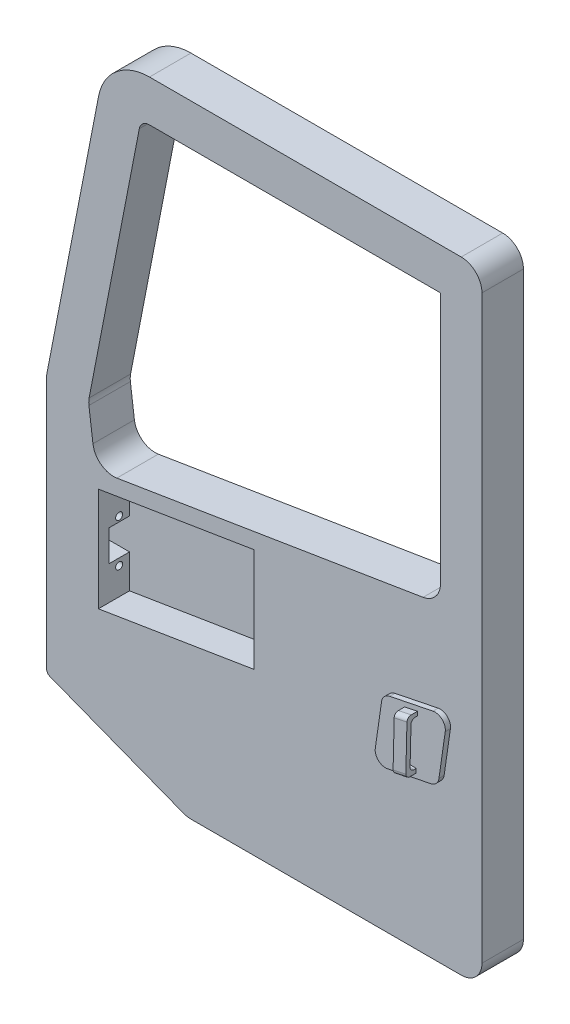
SolidWorks part; units mm, degrees
ref_plane "Front Plane" through (0, 0, 0) normal (0, 0, 1) x (1, 0, 0)
ref_plane "Top Plane" through (0, 0, 0) normal (0, 1, 0) x (1, 0, 0)
ref_plane "Right Plane" through (0, 0, 0) normal (1, 0, 0) x (0, 0, -1)
sketch "Sketch2" plane through (0, 0, 0) normal (0, 0, 1) x (1, 0, 0)
  line L0 (-405.8971, 659.2079) -> (-532.5433, 7.5919)
  line L1 (-179.7693, -762.022) -> (482.6, -762.022)
  line L3 (-281.2299, 761.978) -> (482.6, 761.978)
  line L4 (533.4, -711.222) -> (533.4, 711.178)
  line L5 (-459.8603, -656.939) -> (-452.0517, -645.784) construction
  line L6 (-417.9715, 597.0829) -> (44.1715, -63.1001) construction
  line L8 (-525.2852, -631.9868) -> (-198.1028, -758.5984)
  line L9 (-306.1633, 639.824) -> (-429.1581, 6.9955)
  line L10 (-429.6693, -9.2299) -> (-419.7789, -85.4932)
  line L14 (-281.2299, 660.378) -> (431.8, 660.378)
  line L15 (389.1621, -6.9365) -> (-361.2381, -129.0997)
  line L16 (431.7995, 43.2033) -> (431.8, 660.378)
  line L17 (431.8, -660.422) -> (431.8, 660.378) construction
  line L18 (-170.2829, -660.422) -> (431.8, -660.422) construction
  line L20 (-354.461, -589.1496) -> (-170.2829, -660.422) construction
  line L21 (-55.5325, -79.3316) -> (521.0599, 744.3665) construction
  line L22 (-306.1633, 639.824) -> (-430.7268, -1.0758) construction
  line L23 (-430.7268, -1.0758) -> (-354.461, -589.1496) construction
  line L24 (-416.9351, -673.9156) -> (-198.1028, -758.5984) construction
  line L25 (-179.7693, -762.022) -> (482.6, -762.022)
  line L27 (-281.2299, 761.978) -> (482.6, 761.978)
  line L28 (533.4, -711.222) -> (533.4, 711.178)
  line L29 (-459.8603, -656.939) -> (521.0599, 744.3665) construction
  line L30 (-417.9715, 597.0829) -> (521.0843, -744.3822) construction
  line L31 (-533.4018, 0.6529) -> (-448.7537, -652.0554) construction
  line L34 (-281.2299, 761.978) -> (482.6, 761.978)
  line L35 (-533.4018, 0.6529) -> (-533.4018, -620.1427)
  line L36 (-179.7693, -762.022) -> (482.6, -762.022)
  line L37 (533.4, 711.178) -> (533.4, -711.222)
  line L38 (-417.9715, 597.0829) -> (521.0843, -744.3822) construction
  line L39 (-460.0617, -657.2267) -> (521.0599, 744.3665) construction
  arc A0 (-405.8971, 659.2079) -> (-281.2299, 761.978) centre (-281.2299, 634.978) cw
  arc A2 (-532.5433, 7.5919) -> (-533.4018, 0.6529) centre (-482.6765, -2.1001) ccw
  arc A3 (533.4, 711.178) -> (482.6, 761.978) centre (482.6, 711.178) ccw
  arc A4 (482.6, -762.022) -> (533.4, -711.222) centre (482.6, -711.222) ccw
  arc A5 (-198.1028, -758.5984) -> (-179.7693, -762.022) centre (-179.7693, -711.222) ccw
  arc A7 (-354.461, -589.1496) -> (-354.461, -589.1496) centre (-354.461, -589.1496) ccw
  arc A8 (-170.2829, -660.422) -> (-170.2829, -660.422) centre (-170.2829, -660.422) ccw
  arc A9 (431.8, -660.422) -> (431.8, -660.422) centre (431.8, -660.422) ccw
  arc A10 (431.8, 660.378) -> (431.8, 660.378) centre (431.8, 660.378) ccw
  arc A11 (-306.1633, 639.824) -> (-281.2299, 660.378) centre (-281.2299, 634.978) cw
  arc A12 (-429.1581, 6.9955) -> (-429.6693, -9.2299) centre (-379.2912, -2.6964) ccw
  arc A13 (-430.7268, -1.0758) -> (-430.7268, -1.0758) centre (-430.7268, -1.0758) ccw construction
  arc A14 (431.7995, 43.2033) -> (389.1621, -6.9365) centre (380.9995, 43.2034) cw
  arc A15 (-419.7789, -85.4932) -> (-361.2381, -129.0997) centre (-369.4008, -78.9598) ccw
  arc A16 (-448.7537, -652.0554) -> (-416.9351, -673.9156) centre (-390.71, -601.6569) ccw construction
  arc A17 (-533.4018, -620.1427) -> (-525.2852, -631.9868) centre (-520.7018, -620.1427) ccw
  point P0 (0, 0)
  point P16 (-533.4, -0.0244)
  point P56 (0, 0)
  point P61 (0, 0)
  dimension "D3" = 127
  dimension "D5" = 50.8
  dimension "D6" = 50.8
  dimension "D8" = 50.8
  dimension "D2" = 12.7
  dimension "D1" = 1066.8
  dimension "D4" = 1524
  dimension "D7" = 101.6
extrude "Boss-Extrude1" add sketch "Sketch2" along normal mid plane 101.6 contours L8 A5 L1 A4 L4 A3 L3 A0 L0 A2 A15 L10 A12 L9 A11 L14 L16 A14 L15 region at (29.3865, -188.1823, 0)
sketch "Sketch3" plane through (0, 0, 50.8) normal (0, 0, 1) x (1, 0, 0)
  line L0 (320.1959, -245.101) -> (425.9265, -223.6716)
  line L3 (314.9201, -401.6691) -> (420.6507, -380.2397)
  line L4 (456.113, -252.1835) -> (440.7462, -358.9639)
  line L5 (300.1004, -266.3768) -> (284.7336, -373.1572)
  line L6 (310.4001, -194.8067) -> (287.3499, -354.9772) construction
  line L7 (-487.6326, -408.8312) -> (533.4008, -201.8888) construction
  line L8 (-457.3598, -558.1943) -> (563.6737, -351.2518) construction
  line L9 (461.2461, -216.515) -> (438.1959, -376.6855) construction
  line L10 (373.0612, -234.3863) -> (367.7854, -390.9544) construction
  line L11 (360.2667, -236.9795) -> (354.9908, -393.5476)
  line L12 (385.8558, -231.7931) -> (380.58, -388.3612)
  line L13 (360.3684, -233.9586) -> (355.0926, -390.5267) construction
  line L14 (385.754, -234.814) -> (380.4782, -391.3821) construction
  arc A0 (300.1004, -266.3768) -> (320.1959, -245.101) centre (325.2414, -269.9949) cw
  arc A1 (284.7336, -373.1572) -> (314.9201, -401.6691) centre (309.8746, -376.7752) ccw
  arc A2 (440.7462, -358.9639) -> (420.6507, -380.2397) centre (415.6052, -355.3458) cw
  arc A3 (456.113, -252.1835) -> (425.9265, -223.6716) centre (430.972, -248.5655) ccw
  dimension "D3" = 25.4
  dimension "D1" = 152.4
  dimension "D2" = 152.4
  dimension "D4" = 12.7
  dimension "D5" = 12.7
extrude "Boss-Extrude2" add sketch "Sketch3" along normal blind 12.7 contours L5 A1 L3 L11 L0 A0 | L4 A3 L0 L12 L3 A2 | L12 L0 L11 L3 region at (325.2101, -323.7797, 50.8) region at (370.4233, -312.6704, 50.8) region at (415.6365, -301.561, 50.8)
sketch "Sketch5" plane through (0, 0, 50.8) normal (0, 0, 1) x (1, 0, 0)
  line L0 (-429.6693, -9.2299) -> (-419.7789, -85.4932) construction
  line L1 (389.1621, -6.9365) -> (-361.2381, -129.0997) construction
  line L2 (431.7995, 43.2033) -> (431.8, 660.378) construction
  line L3 (-281.2299, 660.378) -> (431.8, 660.378) construction
  line L4 (-306.1633, 639.824) -> (-429.1581, 6.9955) construction
  line L5 (-429.6693, -9.2299) -> (-419.7789, -85.4932)
  line L6 (-179.7693, -762.022) -> (482.6, -762.022)
  line L12 (-179.7693, -762.022) -> (482.6, -762.022)
  line L18 (389.1621, -6.9365) -> (-361.2381, -129.0997)
  line L19 (431.7995, 43.2033) -> (431.8, 660.378)
  line L20 (-281.2299, 660.378) -> (431.8, 660.378)
  line L21 (-306.1633, 639.824) -> (-429.1581, 6.9955)
  line L28 (387.9598, -243.0291) -> (384.7172, -375.8602)
  line L29 (353.4927, -382.1888) -> (356.7353, -249.3577)
  line L30 (387.9598, -243.0291) -> (356.7353, -249.3577)
  line L31 (384.7172, -375.8602) -> (353.4927, -382.1888)
  line L32 (320.1959, -245.101) -> (425.9265, -223.6716) construction
  line L33 (314.9201, -401.6691) -> (420.6507, -380.2397) construction
  line L34 (320.1959, -245.101) -> (425.9265, -223.6716) construction
  line L35 (314.9201, -401.6691) -> (420.6507, -380.2397) construction
  arc A0 (-419.7789, -85.4932) -> (-361.2381, -129.0997) centre (-369.4008, -78.9598) ccw construction
  arc A1 (389.1621, -6.9365) -> (431.7995, 43.2033) centre (380.9995, 43.2034) ccw construction
  arc A2 (-281.2299, 660.378) -> (-306.1633, 639.824) centre (-281.2299, 634.978) ccw construction
  arc A3 (-429.1581, 6.9955) -> (-429.6693, -9.2299) centre (-379.2912, -2.6964) ccw construction
  arc A4 (-419.7789, -85.4932) -> (-361.2381, -129.0997) centre (-369.4008, -78.9598) ccw
  arc A5 (389.1621, -6.9365) -> (431.7995, 43.2033) centre (380.9995, 43.2034) ccw
  arc A18 (-281.2299, 660.378) -> (-306.1633, 639.824) centre (-281.2299, 634.978) ccw
  arc A19 (-429.1581, 6.9955) -> (-429.6693, -9.2299) centre (-379.2912, -2.6964) ccw
  dimension "D2" = 11.43
  dimension "D3" = 11.43
  dimension "D1" = 0
extrude "Boss-Extrude4" add sketch "Sketch5" along normal blind 38.1 contours L31 L28 L30 L29 region at (370.7262, -312.609, 50.8)
sketch "Sketch6" plane through (393.6581, -9.61, 0) normal (0.9997, -0.0244, 0) x (0, 0, -1)
  line L9 (-63.5, -356.1994) -> (-78.74, -356.1994)
  line L10 (-78.74, -356.1994) -> (-78.74, -243.6487)
  line L11 (-78.74, -243.6487) -> (-63.5, -243.6487)
  line L12 (-63.5, -356.1994) -> (-78.74, -356.1994)
  line L13 (-78.74, -356.1994) -> (-78.74, -243.6487)
  line L14 (-78.74, -243.6487) -> (-63.5, -243.6487)
  line M5 (-63.5, -366.3594) -> (-63.5, -233.4887)
  dimension "D1" = 10.16
extrude "Cut-Extrude6" cut sketch "Sketch6" against normal through all and the other way through all contours L14 L13 L12 M5 region at (386.3385, -309.4447, 71.12)
fillet "Fillet5" radius 10.16 4 edges at (369.1049, -379.0245, 88.9) (369.4394, -365.3242, 78.74) (372.1861, -252.8071, 78.74) (372.3476, -246.1934, 88.9)
sketch "Sketch7" plane through (-533.4018, 59.3738, 0) normal (1, 0, 0) x (0, 0, 1)
  line L0 (0, 821.3958) -> (0, -702.6042) construction
  line L1 (50.8, 821.3958) -> (-50.8, 821.3958) construction
  line L2 (50.8, -702.6042) -> (-50.8, -702.6042) construction
  line L3 (50.8, 58.7209) -> (-50.8, 58.7209) construction
  line L4 (-31.75, 84.1209) -> (31.75, 84.1209)
  line L5 (-31.75, 84.1209) -> (-31.75, 236.5209)
  line L6 (-31.75, 236.5209) -> (31.75, 236.5209)
  line L11 (31.75, 84.1209) -> (31.75, 236.5209)
  line L12 (-31.75, 84.1209) -> (31.75, 236.5209) construction
  line L13 (-31.75, 236.5209) -> (31.75, 84.1209) construction
  line L21 (-31.75, 642.9209) -> (31.75, 642.9209)
  line L28 (-31.75, 642.9209) -> (-31.75, 490.5209)
  line L29 (-31.75, 490.5209) -> (31.75, 490.5209)
  line L30 (31.75, 642.9209) -> (31.75, 490.5209)
  line L31 (-31.75, 642.9209) -> (31.75, 490.5209) construction
  line L32 (-31.75, 490.5209) -> (31.75, 642.9209) construction
  point P6 (0, 160.3209)
  point P13 (0, 566.7209)
  dimension "D1" = 63.5
  dimension "D2" = 152.4
  dimension "D3" = 25.4
  dimension "D4" = 254
extrude "Boss-Extrude5" add sketch "Sketch7" against normal blind 12.7
sketch "Sketch13" plane through (-546.1018, 0, 0) normal (-1, 0, 0) x (0, 0, 1)
  line L0 (0, -24.7471) -> (0, -177.1471) construction
  line L3 (-31.75, -24.7471) -> (31.75, -24.7471) construction
  line L6 (31.75, -177.1471) -> (-31.75, -177.1471) construction
  line L9 (31.75, -100.9471) -> (-31.75, -100.9471) construction
  line L10 (31.75, -24.7471) -> (31.75, -177.1471) construction
  line L11 (-31.75, -177.1471) -> (-31.75, -24.7471) construction
  line L12 (0, -431.1471) -> (0, -583.5471) construction
  line L13 (-31.75, -431.1471) -> (31.75, -431.1471) construction
  line L14 (31.75, -583.5471) -> (-31.75, -583.5471) construction
  line L15 (31.75, -507.3471) -> (-31.75, -507.3471) construction
  line L16 (31.75, -431.1471) -> (31.75, -583.5471) construction
  line L17 (-31.75, -583.5471) -> (-31.75, -431.1471) construction
  circle A4 centre (0, -50.1471) radius 11.43
  circle A6 centre (0, -151.7471) radius 11.43
  circle A7 centre (0, -456.5471) radius 11.43
  circle A8 centre (0, -558.1471) radius 11.43
  dimension "D1" = 50.8
  dimension "D2" = 22.86
  dimension "D3" = 50.8
  dimension "D4" = 22.86
extrude "Cut-Extrude7" cut sketch "Sketch13" against normal blind 46.99
sketch "Sketch14" plane through (-533.4018, 0, 0) normal (-1, 0, 0) x (0, 0, 1)
  line L0 (0, 761.978) -> (0, -758.5984) construction
  line L3 (50.8, 761.978) -> (-50.8, 761.978) construction
  line L4 (50.8, -758.5984) -> (-50.8, -758.5984) construction
  line L6 (-25.4, -346.3817) -> (25.4, -346.3817)
  line L7 (-25.4, -346.3817) -> (-25.4, -270.1817)
  line L8 (-25.4, -270.1817) -> (25.4, -270.1817)
  line L9 (25.4, -346.3817) -> (25.4, -270.1817)
  line L10 (-25.4, -346.3817) -> (25.4, -270.1817) construction
  line L11 (-25.4, -270.1817) -> (25.4, -346.3817) construction
  circle A0 centre (0, -257.9183) radius 8.5706
  circle A1 centre (0, -363.1476) radius 8.5706
  point P6 (0, -308.2817)
  dimension "D2" = 76.2
sketch "Sketch16" plane through (0, 0, 50.8) normal (0, 0, 1) x (1, 0, 0)
  line L0 (-406.4018, -175.0538) -> (-25.4018, -113.028)
  line L1 (-406.4018, -175.0538) -> (-406.4018, -429.0538)
  line L2 (-406.4018, -429.0538) -> (-25.4018, -367.028)
  line L3 (-25.4018, -367.028) -> (-25.4018, -113.028)
  line L4 (389.1621, -6.9365) -> (-361.2381, -129.0997) construction
  line L5 (-533.4018, 0.6529) -> (-533.4018, -620.1427) construction
  dimension "D1" = 381
  dimension "D2" = 254
  dimension "D3" = 38.1
  dimension "D4" = 127
extrude "Cut-Extrude8" cut sketch "Sketch16" against normal blind 76.2
extrude "Cut-Extrude9" cut sketch "Sketch14" against normal up to surface (127 mm away) contours A0 | A1 | L7 L8 L9 L6 region at (-533.4018, -257.9183, 0) region at (-533.4018, -363.1476, 0) up to face at (-406.4018, -302.0538, 12.7)
equation "\"doorwidth\"= 42in"
equation "\"D1@Sketch2\"=\"doorwidth\""
equation "\"doorheight\"= 60in"
equation "\"D4@Sketch2\"=\"doorheight\""
equation "\"doorthickness\"= 4in"
equation "\"D1@Boss-Extrude1\"=\"doorthickness\""
equation "\"hingewidth\"= 2.5in"
equation "\"hingeheight\"= 6in"
equation "\"distanceofhinges\"= 10in"
equation "\"actuator slot width\"= 2in"
equation "\"actuator slot height\"= 3in"
equation "\"D2@Sketch14\"=\"actuator slot height\""
equation "\"D1@Sketch14\"=\"actuator slot width\""
equation "\"D1@Sketch7\"=\"hingewidth\""
equation "\"D2@Sketch7\"=\"hingeheight\""
equation "\"D4@Sketch7\"=\"distanceofhinges\""
